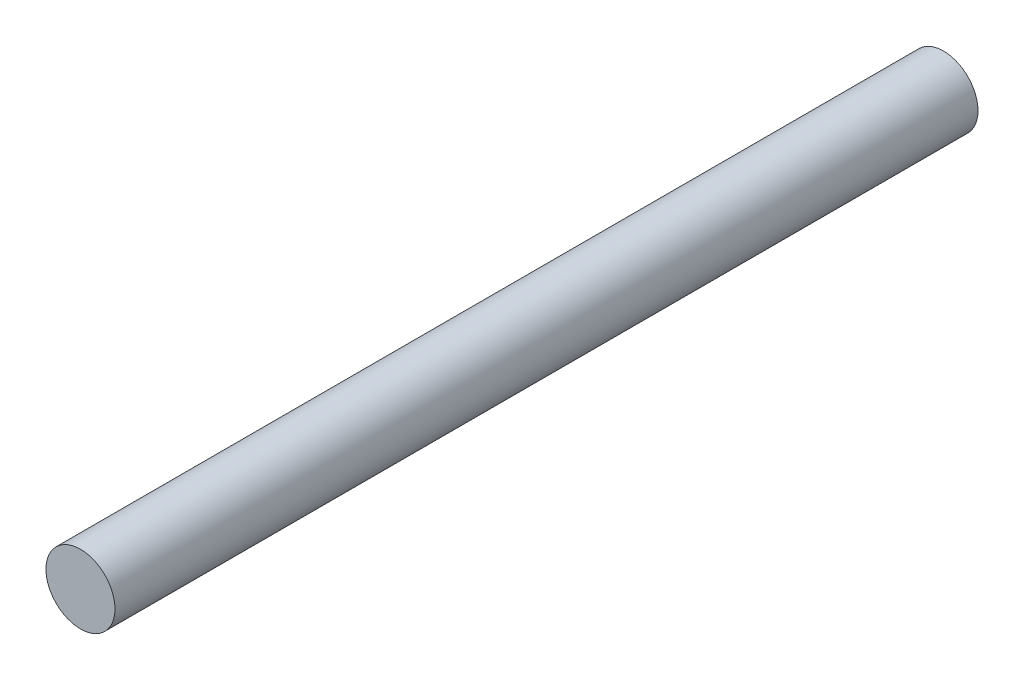
SolidWorks part; units mm, degrees
ref_plane "Front Plane" through (0, 0, 0) normal (0, 0, 1) x (1, 0, 0)
ref_plane "Top Plane" through (0, 0, 0) normal (0, 1, 0) x (1, 0, 0)
ref_plane "Right Plane" through (0, 0, 0) normal (1, 0, 0) x (0, 0, -1)
sketch "Sketch1" plane through (0, 0, 0) normal (0, 0, 1) x (1, 0, 0)
  circle A0 centre (0, 0) radius 2
  dimension "D1" = 4
extrude "Boss-Extrude1" add sketch "Sketch1" along normal blind 25 and the other way blind 25
